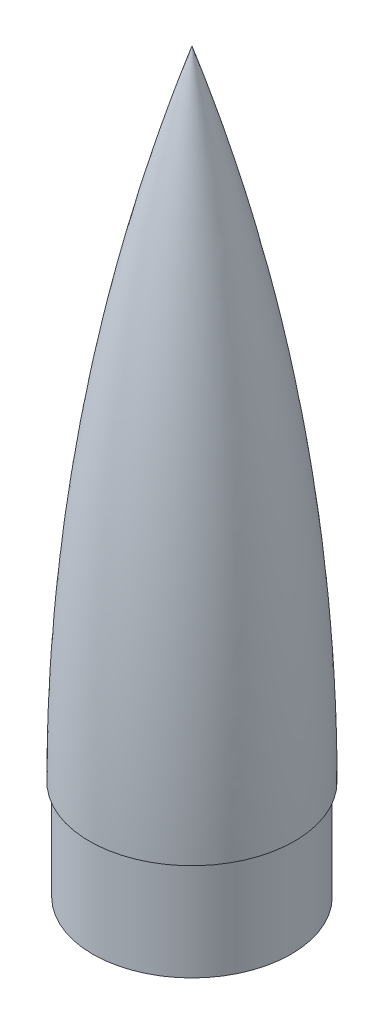
SolidWorks part; units mm, degrees
ref_plane "Front Plane" through (0, 0, 0) normal (0, 0, 1) x (1, 0, 0)
ref_plane "Top Plane" through (0, 0, 0) normal (0, 1, 0) x (1, 0, 0)
ref_plane "Right Plane" through (0, 0, 0) normal (1, 0, 0) x (0, 0, -1)
sketch "Sketch2" plane through (0, 0, 0) normal (0, 0, 1) x (1, 0, 0)
  line L0 (-1295.2984, 0) -> (-1229.8934, 0)
  line L1 (-1229.8934, 0) -> (-1229.8934, 406.399)
  arc A0 (-1229.8934, 406.399) -> (-1295.2984, 0) centre (0, 0) ccw
  dimension "D1" = 2590.5968
  dimension "D2" = 65.405
revolve "Revolve1" add sketch "Sketch2" angle 360 about L1
shell "Shell1" thickness 7.62 removed face at (-1229.8934, 0, -65.405)
sketch "Sketch3" plane through (0, 0, 0) normal (0, -1, 0) x (1, 0, 0)
  circle A0 centre (-1229.8934, 0) radius 63.246
  circle A1 centre (-1229.8934, 0) radius 65.405 construction
  circle A2 centre (-1229.8934, 0) radius 55.626
  dimension "D1" = 126.492
  dimension "D2" = 7.62
extrude "Boss-Extrude1" add sketch "Sketch3" along normal blind 63.5
equation "\"OgiveRadius\"= 50.996in"
equation "\"D1@Sketch2\"=\"OgiveRadius\"*2"
equation "\"InsideDiameter\" = 4.98in"
equation "\"InsideThickness\"= 0.3in"
equation "\"D1@Sketch3\"=\"InsideDiameter\""
equation "\"D2@Sketch3\"=\"InsideThickness\""
equation "\"InsideLength\"= 2.5in"
equation "\"D1@Boss-Extrude1\"=\"InsideLength\""
